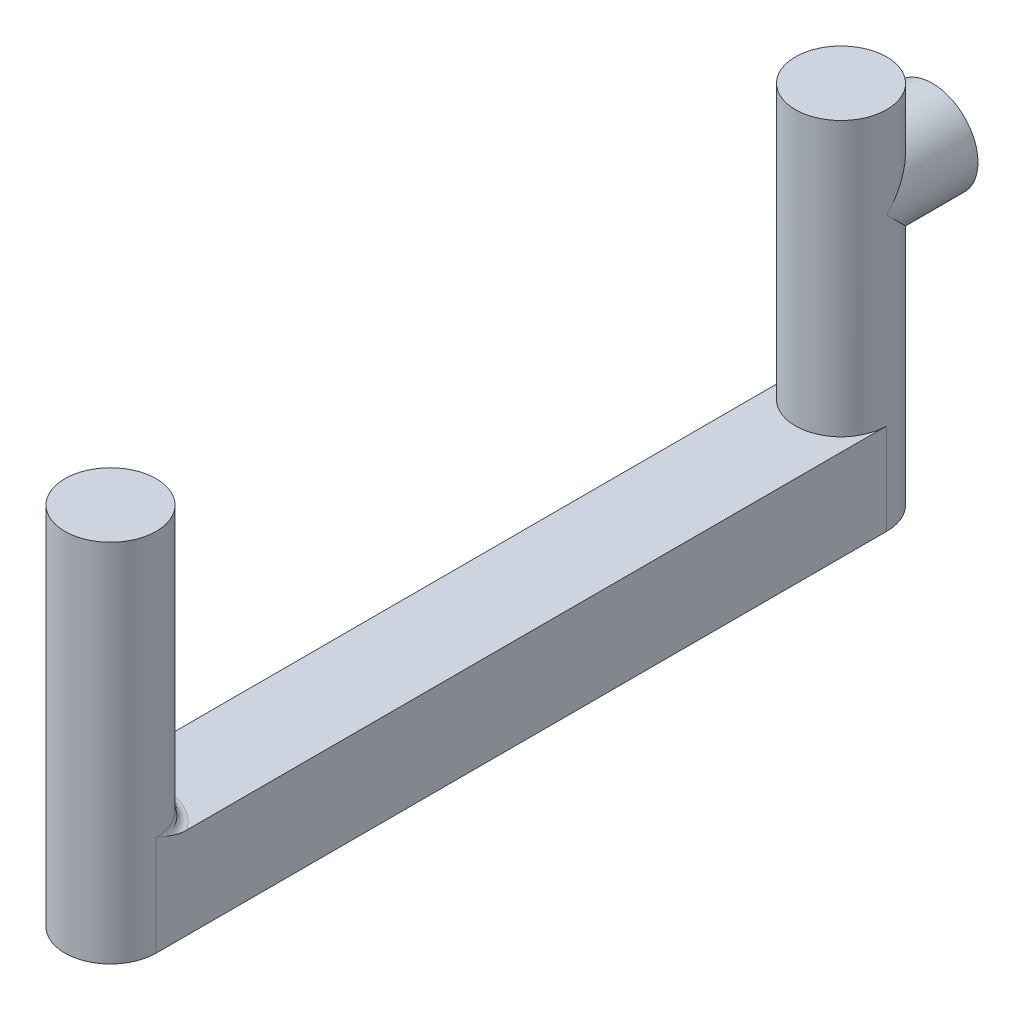
SolidWorks part; units mm, degrees
ref_plane "Front Plane" through (0, 0, 0) normal (0, 0, 1) x (1, 0, 0)
ref_plane "Top Plane" through (0, 0, 0) normal (0, 1, 0) x (1, 0, 0)
ref_plane "Right Plane" through (0, 0, 0) normal (1, 0, 0) x (0, 0, -1)
sketch "Sketch1" plane through (0, 0, 0) normal (0, 1, 0) x (1, 0, 0)
  line L1 (-2.5, 20) -> (2.5, 20)
  line L2 (-2.5, 20) -> (-2.5, 0)
  line L3 (-2.5, 0) -> (2.5, 0)
  line L4 (2.5, 20) -> (2.5, 0)
  dimension "D1" = 5
  dimension "D2" = 20
extrude "Boss-Extrude1" add sketch "Sketch1" along normal blind 5
sketch "Sketch4" plane through (0, 0, 0) normal (0, 1, 0) x (1, 0, 0)
  line L0 (-2.5, 0) -> (2.5, 0) construction
  circle A0 centre (0, 0) radius 2.5
  dimension "D1" = 5
extrude "Boss-Extrude2" add sketch "Sketch4" along normal blind 20
fillet "Fillet1" radius 0.5 1 edges at (0, 5, -2.5)
mirror "Mirror1" about plane through (-2.5, 5, -20) normal (0, 0, 1) of "Boss-Extrude1", "Boss-Extrude2"
sketch "Sketch5" plane through (0, 0, 0) normal (0, 0, 1) x (1, 0, 0)
  line L0 (0, 0) -> (0, 20) construction
  line L1 (2.5, 20) -> (-2.5, 20) construction
  circle A0 centre (0, 15) radius 2.5
  dimension "D1" = 5
  dimension "D2" = 5
extrude "Boss-Extrude4" add sketch "Sketch5" against normal blind 5 from offset 40 offset against normal yes
